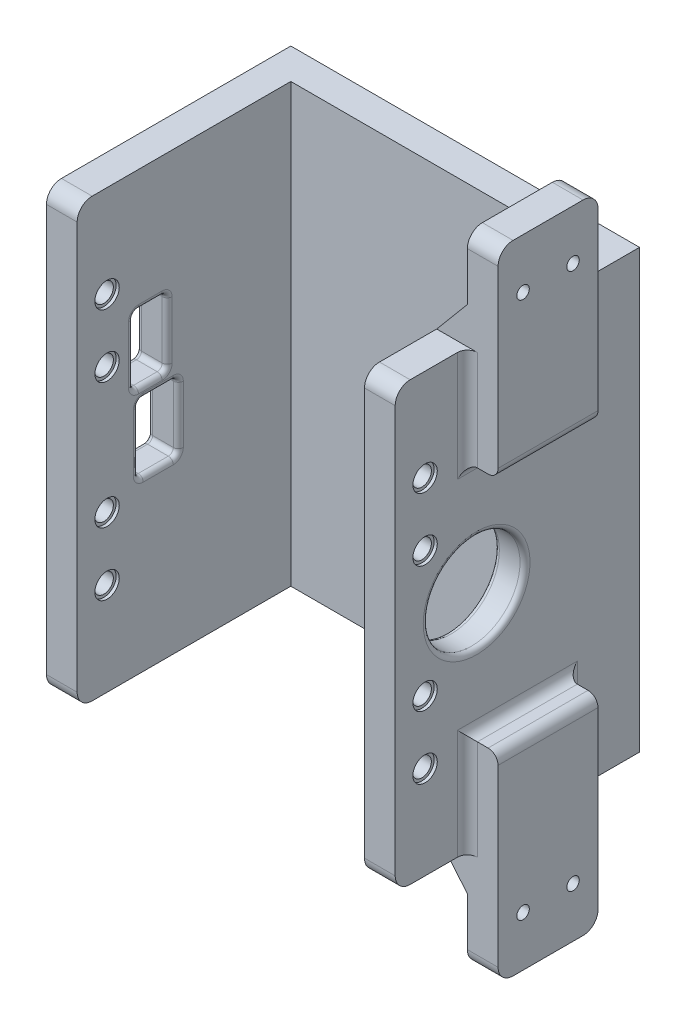
SolidWorks part; units mm, degrees
ref_plane "Front Plane" through (0, 0, 0) normal (0, 0, 1) x (1, 0, 0)
ref_plane "Top Plane" through (0, 0, 0) normal (0, 1, 0) x (1, 0, 0)
ref_plane "Right Plane" through (0, 0, 0) normal (1, 0, 0) x (0, 0, -1)
sketch "Sketch1" plane through (0, 0, 0) normal (1, 0, 0) x (0, 0, -1)
  line L1 (0, 0) -> (55.1, 0)
  line L2 (0, 0) -> (0, 111.1)
  line L3 (0, 111.1) -> (55.1, 111.1)
  line L4 (55.1, 0) -> (55.1, 111.1)
  dimension "D1" = 55.1
  dimension "D2" = 111.1
extrude "Boss-Extrude1" add sketch "Sketch1" along normal blind 7.8
sketch "Sketch2" plane through (0, 0, 0) normal (-1, 0, 0) x (0, 0, 1)
  line L0 (0, 111.1) -> (-47.3, 111.1) construction
  line L1 (-55.1, 111.1) -> (0, 111.1) construction
  line L3 (-47.3, 111.1) -> (-55.1, 111.1)
  line L4 (-47.3, 111.1) -> (-47.3, 0)
  line L5 (-47.3, 0) -> (-55.1, 0)
  line L6 (-55.1, 111.1) -> (-55.1, 0)
  dimension "D1" = 7.8
extrude "Boss-Extrude2" add sketch "Sketch2" along normal blind 73.025 contours L4 L3 L6 L5
sketch "Sketch4" plane through (-73.025, 0, 0) normal (-1, 0, 0) x (0, 0, 1)
  line L1 (-55.1, 111.1) -> (0, 111.1)
  line L2 (-55.1, 111.1) -> (-55.1, 0)
  line L3 (-55.1, 0) -> (0, 0)
  line L4 (0, 111.1) -> (0, 0)
extrude "Boss-Extrude3" add sketch "Sketch4" along normal blind 7.8 contours L2 L1 L4 L3
ref_plane "Plane1" through (-36.5125, 0, 0) normal (-1, 0, 0) x (0, 0, 1)
sketch "Sketch7" plane through (0, 0, 0) normal (0, 0, 1) x (1, 0, 0)
  line L4 (0, 0) -> (7.8, 0)
  line L5 (7.8, 0) -> (7.8, 111.1)
  line L6 (7.8, 111.1) -> (0, 111.1)
  line L7 (0, 111.1) -> (0, 0)
  line L8 (0, 0) -> (7.8, 0)
  line L10 (7.8, 111.1) -> (0, 111.1)
  line L11 (0, 111.1) -> (0, 0)
  line L16 (7.8, 0) -> (7.8, 111.1)
  dimension "D1" = 0
extrude "Boss-Extrude4" add sketch "Sketch7" along normal blind 7 contours L8 L16 L10 L11
sketch "Sketch8" plane through (7.8, 0, 0) normal (1, 0, 0) x (0, 0, -1)
  line L1 (-7, 0) -> (-7, 111.1) construction
  line L2 (-7, 0) -> (55.1, 0) construction
  line L3 (0.6, 30.1777) -> (0.6, 16.5296) construction
  circle A0 centre (0.6, 23.6) radius 3.1
  circle A1 centre (0.6, 23.6) radius 2.4
  circle A2 centre (0.6, 39.6) radius 3.1
  circle A3 centre (0.6, 39.6) radius 2.4
  circle A4 centre (0.6, 87.6) radius 3.1
  circle A5 centre (0.6, 87.6) radius 2.4
  circle A6 centre (0.6, 71.6) radius 3.1
  circle A7 centre (0.6, 71.6) radius 2.4
  dimension "D1" = 6.2
  dimension "D2" = 4.8
  dimension "D5" = 6.2
  dimension "D6" = 4.8
  dimension "D3" = 23.6
  dimension "D4" = 16
  dimension "D7" = 16
  dimension "D8" = 32
  dimension "D9" = 7.6
extrude "Cut-Extrude4" cut sketch "Sketch8" against normal blind 12.7 contours A5 | A7 | A3 | A1 L3 | L3 A1 region at (7.8, 23.6, -1.6186) region at (7.8, 23.6, 0.4186) region at (7.8, 39.6, -0.6) region at (7.8, 87.6, -0.6) region at (7.8, 71.6, -0.6)
extrude "Cut-Extrude5" cut sketch "Sketch8<4>" against normal blind 0.8 contours A4 | A6 | A2 | A0
sketch "Sketch8<4>" plane through (7.8, 0, 0) normal (1, 0, 0) x (0, 0, -1) same geometry as "Sketch8"
sketch "Sketch9" plane through (0, 0, 7) normal (0, 0, 1) x (1, 0, 0)
  line L0 (3.9, 0) -> (3.9, 111.1) construction
  line L1 (0, 0) -> (7.8, 0) construction
  line L2 (7.8, 111.1) -> (0, 111.1) construction
ref_plane "Plane2" through (3.9, 0, 0) normal (1, 0, 0) x (0, 0, -1)
mirror "Mirror1" about plane through (3.9, 0, 0) normal (1, 0, 0) of "Cut-Extrude5"
mirror "Mirror2" about plane through (-36.5125, 0, 0) normal (-1, 0, 0) of "Cut-Extrude4", "Boss-Extrude4", "Mirror1", "Cut-Extrude5"
sketch "Sketch10" plane through (7.8, 0, 0) normal (1, 0, 0) x (0, 0, -1)
  line L1 (-7, 0) -> (55.1, 0) construction
  line L2 (-7, 0) -> (-7, 111.1) construction
  circle A0 centre (13.7, 55.7) radius 12.3
  dimension "D1" = 24.6
  dimension "D2" = 20.7
  dimension "D3" = 55.7
extrude "Cut-Extrude7" cut sketch "Sketch10" against normal up to surface (7.8 mm away) up to face at (0, 87.6, -3.7)
sketch "Sketch11" plane through (-80.825, 0, 0) normal (-1, 0, 0) x (0, 0, 1)
  line L1 (-14.6, 78.8) -> (-8.6, 78.8) construction
  line L2 (-14.6, 78.8) -> (-14.6, 64.2) construction
  line L3 (-14.6, 64.2) -> (-8.6, 64.2) construction
  line L4 (-8.6, 78.8) -> (-8.6, 64.2) construction
  line L5 (-17.435, 58.8) -> (-9.8, 58.8) construction
  line L6 (-17.435, 58.8) -> (-17.435, 44.2) construction
  line L7 (-17.435, 44.2) -> (-9.8, 44.2) construction
  line L8 (-9.8, 58.8) -> (-9.8, 44.2) construction
  line L9 (-55.1, 0) -> (7, 0) construction
  line L10 (-15.87, 80.07) -> (-7.33, 80.07)
  line L11 (-7.33, 80.07) -> (-7.33, 62.93)
  line L12 (-15.87, 62.93) -> (-7.33, 62.93)
  line L13 (-15.87, 80.07) -> (-15.87, 62.93)
  line L14 (-8.53, 60.07) -> (-8.53, 42.93)
  line L15 (-18.705, 42.93) -> (-8.53, 42.93)
  line L16 (-18.705, 60.07) -> (-18.705, 42.93)
  line L17 (-18.705, 60.07) -> (-8.53, 60.07)
  line L18 (7, 0) -> (7, 111.1) construction
  dimension "D1" = 14.6
  dimension "D2" = 6
  dimension "D3" = 15.6
  dimension "D4" = 64.2
  dimension "D5" = 14.6
  dimension "D6" = 7.635
  dimension "D7" = 16.8
  dimension "D8" = 44.2
  dimension "D9" = 1.27
  dimension "D10" = 1.27
extrude "Cut-Extrude8" cut sketch "Sketch11" against normal up to surface (7.8 mm away) contours L10 L11 L12 L13 | L14 L15 L16 L17 up to face at (-73.025, 87.6, -3.7)
fillet "Fillet1" radius 1.27 26 edges at (-73.025, 51.5, -18.705) (-80.825, 51.5, -18.705) (-73.025, 42.93, -13.6175) (-80.825, 42.93, -13.6175) (-76.925, 42.93, -18.705) (-80.825, 51.5, -8.53) (-76.925, 42.93, -8.53) (-73.025, 51.5, -8.53) (-76.925, 60.07, -18.705) (-80.825, 60.07, -13.6175) (-76.925, 60.07, -8.53) (-73.025, 60.07, -13.6175) (-73.025, 62.93, -11.6) (-80.825, 62.93, -11.6) (-80.825, 71.5, -7.33) (-76.925, 62.93, -7.33) (-73.025, 71.5, -7.33) (-80.825, 80.07, -11.6) (-76.925, 80.07, -7.33) (-73.025, 80.07, -11.6) (-73.025, 71.5, -15.87) (-76.925, 62.93, -15.87) (-80.825, 71.5, -15.87) (-76.925, 80.07, -15.87) (0, 55.7, -1.4) (7.8, 55.7, -26)
sketch "Sketch12" plane through (0, 111.1, 0) normal (0, 1, 0) x (1, 0, 0)
  line L0 (7.8, 55.1) -> (7.8, -7) construction
  line L1 (7.8, 36.75) -> (15.6, 36.75)
  line L2 (7.8, 36.75) -> (7.8, 11.35)
  line L3 (7.8, 11.35) -> (15.6, 11.35)
  line L4 (15.6, 36.75) -> (15.6, 11.35)
  point P6 (7.8, 24.05)
  point P7 (7.8, 24.05)
  dimension "D1" = 25.4
  dimension "D2" = 7.8
extrude "Boss-Extrude5" add sketch "Sketch12" along normal mid plane 50.8
sketch "Sketch13" plane through (7.8, 0, 0) normal (1, 0, 0) x (0, 0, -1)
  line L0 (29.7, 111.1) -> (29.7, 0) construction
  line L1 (-7, 0) -> (55.1, 0) construction
  line L2 (55.1, 0) -> (55.1, 111.1) construction
  point P5 (29.7, 55.55)
  dimension "D1" = 25.4
ref_plane "Plane3" through (0, 55.55, 0) normal (0, 1, 0) x (1, 0, 0)
sketch "Sketch14" plane through (0, 0, 0) normal (-1, 0, 0) x (0, 0, 1)
  line L0 (-36.75, 136.5) -> (-11.35, 136.5) construction
  line L1 (-55.1, 111.1) -> (7, 111.1) construction
  line L2 (-36.75, 136.5) -> (-36.75, 111.1) construction
  circle A0 centre (-30.4, 123.8) radius 1.5875
  circle A1 centre (-17.7, 123.8) radius 1.5875
  dimension "D1" = 3.175
  dimension "D2" = 3.175
  dimension "D3" = 12.7
  dimension "D4" = 12.7
  dimension "D5" = 12.7
  dimension "D6" = 6.35
extrude "Cut-Extrude9" cut sketch "Sketch14" against normal through all
mirror "Mirror6" about plane through (0, 55.55, 0) normal (0, 1, 0) of "Cut-Extrude9", "Boss-Extrude5"
chamfer "Chamfer2" distance 7.8 angle 50 2 edges at (7.8, 111.1, -24.05) (7.8, 0, -24.05) first distance on face at (-27.65, 111.1, -22.49) first distance on face at (-27.65, 0, -22.49)
fillet "Fillet3" radius 3.81 8 edges at (-76.925, 0, 7) (-76.925, 111.1, 7) (3.9, 111.1, 7) (3.9, 0, 7) (11.7, -25.4, -36.75) (11.7, -25.4, -11.35) (11.7, 136.5, -36.75) (11.7, 136.5, -11.35)
fillet "Fillet4" radius 2.54 8 edges at (7.8, 98.4, -36.75) (7.8, 98.4, -11.35) (7.8, 85.7, -24.05) (15.6, 85.7, -24.05) (15.6, 25.4, -24.05) (7.8, 12.7, -11.35) (7.8, 25.4, -24.05) (7.8, 12.7, -36.75)
